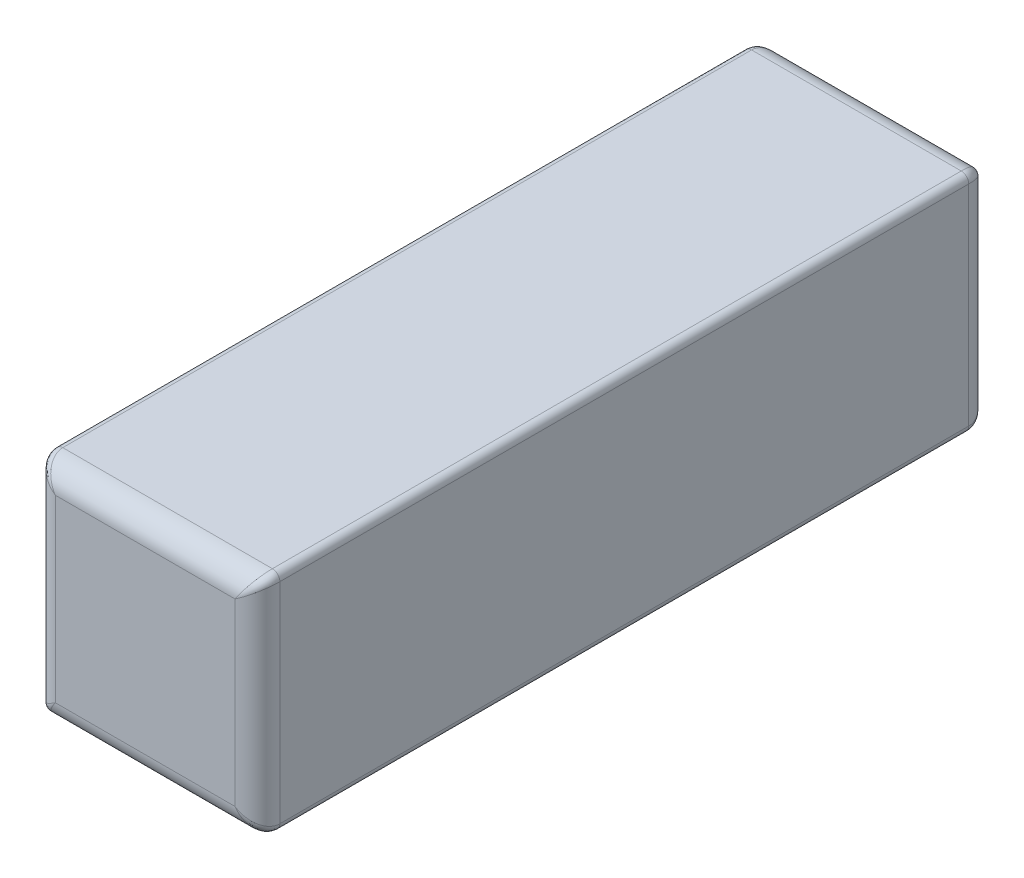
SolidWorks part; units mm, degrees
ref_plane "正面" through (0, 0, 0) normal (0, 0, 1) x (1, 0, 0)
ref_plane "平面" through (0, 0, 0) normal (0, 1, 0) x (1, 0, 0)
ref_plane "右側面" through (0, 0, 0) normal (1, 0, 0) x (0, 0, -1)
sketch "ｽｹｯﾁ1" plane through (0, 0, 0) normal (0, 0, 1) x (1, 0, 0)
  line L1 (-15, 15) -> (15, 15)
  line L2 (-15, 15) -> (-15, -15)
  line L3 (-15, -15) -> (15, -15)
  line L4 (15, 15) -> (15, -15)
  line L5 (-15, 15) -> (15, -15) construction
  line L6 (-15, -15) -> (15, 15) construction
  point P0 (0, 0)
  dimension "D1" = 30
extrude "ﾎﾞｽ - 押し出し1" add sketch "ｽｹｯﾁ1" along normal mid plane 98
fillet "ﾌｨﾚｯﾄ1" radius 1 4 edges at (15, -15, 0) (-15, -15, 0) (-15, 15, 0) (15, 15, 0)
fillet "ﾌｨﾚｯﾄ2" radius 3 16 edges at (14.7071, 14.7071, -49) (0, 15, -49) (-14.7071, 14.7071, -49) (-15, 0, -49) (-14.7071, -14.7071, -49) (0, -15, -49) (14.7071, -14.7071, -49) (15, 0, -49) (-14.7071, -14.7071, 49) (-15, 0, 49) (-14.7071, 14.7071, 49) (0, 15, 49) (14.7071, 14.7071, 49) (15, 0, 49) (14.7071, -14.7071, 49) (0, -15, 49)
